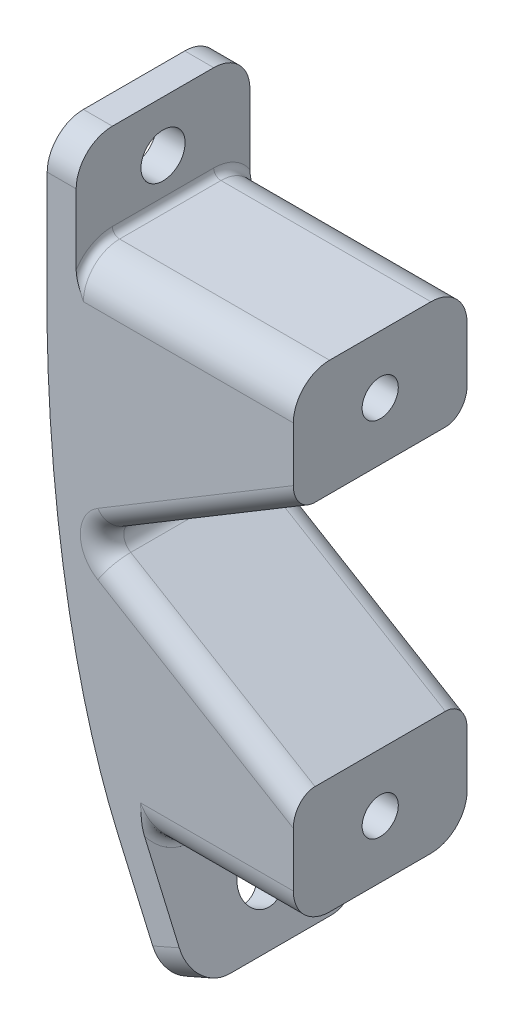
SolidWorks part; units mm, degrees
ref_plane "Front Plane" through (0, 0, 0) normal (0, 0, 1) x (1, 0, 0)
ref_plane "Top Plane" through (0, 0, 0) normal (0, 1, 0) x (1, 0, 0)
ref_plane "Right Plane" through (0, 0, 0) normal (1, 0, 0) x (0, 0, -1)
sketch "Sketch2" plane through (0, 0, 0) normal (1, 0, 0) x (0, 0, -1)
  line L0 (12, 98) -> (12, 0) construction
  line L1 (0, 0) -> (24, 0)
  line L2 (0, 0) -> (0, 98)
  line L3 (0, 98) -> (24, 98)
  line L4 (24, 0) -> (24, 98)
  line L5 (0, 49) -> (24, 49) construction
  circle A0 centre (12, 88) radius 3.05
  dimension "D3" = 6.1
  dimension "D4" = 39
  dimension "D1" = 98
  dimension "D2" = 24
extrude "Boss-Extrude1" add sketch "Sketch2" along normal blind 4
sketch "Sketch3" plane through (4, 0, 0) normal (1, 0, 0) x (0, 0, -1)
  line L0 (0, 98) -> (0, 0) construction
  line L1 (0, 82) -> (24, 82)
  line L2 (0, 82) -> (0, 16)
  line L3 (0, 16) -> (24, 16)
  line L4 (24, 82) -> (24, 16)
  line L5 (24, 0) -> (24, 98) construction
  line L6 (0, 49) -> (24, 49) construction
  line L7 (12, 98) -> (12, 0) construction
  line L8 (24, 98) -> (0, 98) construction
  line L9 (0, 0) -> (24, 0) construction
  line L10 (24, 0) -> (24, 98) construction
  dimension "D1" = 66
extrude "Boss-Extrude2" add sketch "Sketch3" along normal blind 30
sketch "Sketch13" plane through (4, 0, 0) normal (1, 0, 0) x (0, 0, -1)
  line L0 (24, 82) -> (24, 98) construction
  line L1 (0, 98) -> (24, 98)
  line L2 (0, 98) -> (0, 95)
  line L3 (0, 95) -> (24, 95)
  line L4 (24, 98) -> (24, 95)
  circle A0 centre (12, 88) radius 3.05 construction
  dimension "D1" = 7
extrude "Cut-Extrude6" cut sketch "Sketch13" against normal through all
sketch "Sketch12" plane through (4, 0, 0) normal (1, 0, 0) x (0, 0, -1)
  circle A0 centre (12, 88) radius 5.25 construction
  dimension "D1" = 10.5
sketch "Sketch4" plane through (34, 0, 0) normal (1, 0, 0) x (0, 0, -1)
  line L0 (12, 82) -> (12, 16) construction
  line L1 (24, 82) -> (0, 82) construction
  line L2 (0, 16) -> (24, 16) construction
  line L3 (0, 49) -> (24, 49) construction
  line L4 (0, 82) -> (0, 16) construction
  line L5 (24, 16) -> (24, 82) construction
  circle A0 centre (12, 74) radius 2.5
  circle A1 centre (12, 24) radius 2.5
  dimension "D1" = 5
  dimension "D2" = 50
extrude "Cut-Extrude1" cut sketch "Sketch4" against normal through all both and the other way through all
sketch "Sketch5" plane through (0, 0, 0) normal (-1, 0, 0) x (0, 0, 1)
  line L0 (-24, 47.5) -> (0, 47.5) construction
  line L1 (-9.7772, 77.85) -> (-14.2228, 77.85)
  line L2 (-14.2228, 77.85) -> (-16.4456, 74)
  line L3 (-16.4456, 74) -> (-14.2228, 70.15)
  line L4 (-14.2228, 70.15) -> (-9.7772, 70.15)
  line L5 (-9.7772, 70.15) -> (-7.5544, 74)
  line L6 (-7.5544, 74) -> (-9.7772, 77.85)
  line L7 (-24, 0) -> (-24, 95) construction
  line L8 (0, 95) -> (0, 0) construction
  line L16 (-9.7772, 27.85) -> (-14.2228, 27.85)
  line L17 (-14.2228, 27.85) -> (-16.4456, 24)
  line L18 (-16.4456, 24) -> (-14.2228, 20.15)
  line L19 (-14.2228, 20.15) -> (-9.7772, 20.15)
  line L20 (-9.7772, 20.15) -> (-7.5544, 24)
  line L21 (-7.5544, 24) -> (-9.7772, 27.85)
  circle A0 centre (-12, 74) radius 3.85 construction
  circle A2 centre (-12, 24) radius 3.85 construction
  dimension "D1" = 7.7
  dimension "D2" = 7.7
extrude "Cut-Extrude2" cut sketch "Sketch5" against normal offset from surface (26 mm away) 8 up to face at (34, 74, -14.5)
sketch "Sketch8" plane through (0, 0, 0) normal (0, 0, 1) x (1, 0, 0)
  line L0 (4, 88.0223) -> (4, -6.0183) construction
  line L1 (0, 82) -> (4, 82)
  line L2 (34, 16) -> (4, 16) construction
  line L4 (29.8923, 0) -> (0, 0)
  line L5 (0, 0) -> (0, 82)
  line L7 (29.8923, 76) -> (29.8923, 0) construction
  line L8 (29.8923, 76) -> (4, 76) construction
  line L9 (4, 82) -> (4, 76)
  line L10 (14, 16) -> (22.1491, -2.5965) construction
  line L11 (0, 95) -> (0, 0) construction
  ellipse E0 centre (29.8923, 76) end of major axis (29.8923, 0) minor radius 25.8923 (4, 76) -> (29.8923, 0) ccw
  point P23 (14, 16)
  dimension "D1" = 60
  dimension "D2" = 10
extrude "Cut-Extrude4" cut sketch "Sketch8" against normal through all
sketch "Sketch10" plane through (0, 0, 0) normal (0, 0, 1) x (1, 0, 0)
  line L6 (0, 95) -> (0, 82) construction
  line L22 (16.5831, 0.1392) -> (20.2468, 1.7446)
  line L23 (20.2468, 1.7446) -> (14, 16)
  line L24 (34, 49) -> (0, 49) construction
  line L25 (34, 82) -> (34, 16) construction
  line L28 (4, 95) -> (4, 82) construction
  line L29 (9.7204, 15.8001) -> (16.5831, 0.1392)
  line L32 (4, 82) -> (4, 76)
  line L33 (14, 16) -> (34, 16)
  line L34 (34, 16) -> (34, 82)
  line L35 (34, 82) -> (4, 82)
  line L36 (4, 82) -> (4, 76)
  line L41 (0, 82) -> (-0.0395, 77.0883)
  line L44 (4, 82) -> (0, 82)
  ellipse E0 centre (29.8923, 76) end of major axis (29.8923, 0) minor radius 25.8923 (4, 76) -> (14, 16) ccw construction
  ellipse E2 centre (29.8923, 76) end of major axis (29.8923, 0) minor radius 25.8923 (4, 76) -> (14, 16) ccw
  ellipse E3 centre (29.8923, 76) end of major axis (29.8923, 0) minor radius 25.8923 (4, 76) -> (14, 16) ccw
  spline S1 degree 3 poles (-0.0395, 77.0883) (-0.0828, 71.7041) (0.0617, 66.3402) (0.7432, 55.6552) (1.2791, 50.334) (2.4388, 42.3908) (2.8853, 39.7496) (3.9207, 34.4826) (4.5095, 31.8561) (5.8674, 26.6259) (6.6313, 24.0405) (8.1733, 19.5712) (8.9011, 17.6697) (9.7204, 15.8001) knots 0 0 0 0 0.25 0.25 0.5 0.5 0.625 0.625 0.75 0.75 0.875 0.875 0.969487 0.969487 0.969487 0.969487
  point P19 (17.4373, 8.156)
  point P30 (5.689, 49)
  dimension "D3" = 7
  dimension "D5" = 42.5
  dimension "D6" = 8.564
  dimension "D1" = 4
  dimension "D8" = 0
extrude "Boss-Extrude3" add sketch "Sketch10" against normal up to surface (24 mm away) up to face at (17.5268, 53.7205, -24)
fillet "Fillet1" radius 5 4 edges at (18.415, 0.9419, -24) (18.415, 0.9419, 0) (2, 95, -24) (2, 95, 0)
fillet "Fillet2" radius 5 4 edges at (24, 16, -24) (24, 16, 0) (19, 82, -24) (19, 82, 0)
sketch "Sketch7" plane through (0, 0, -24) normal (0, 0, -1) x (-1, 0, 0)
  line L0 (-34, 66) -> (-5.689, 49)
  line L1 (-34, 21) -> (-34, 77) construction
  line L3 (-5.689, 49) -> (-34, 32)
  line L4 (-34, 32) -> (-34, 66)
  line L5 (-34, 49) -> (-5.689, 49) construction
  dimension "D1" = 34
extrude "Cut-Extrude3" cut sketch "Sketch7" against normal through all
sketch "Sketch11" plane through (13.9629, 6.1186, 0) normal (-0.9159, -0.4014, 0) x (0, 0, 1)
  line L0 (-12, -6.5284) -> (-12, 0.4716) construction
  line L1 (-19, -6.5284) -> (-5, -6.5284) construction
  line L2 (0, 0.4716) -> (-12, 0.4716) construction
  circle A0 centre (-12, 0.4716) radius 3
  dimension "D1" = 6
extrude "Cut-Extrude5" cut sketch "Sketch11" against normal up to next
fillet "Fillet3" [suppressed] radius 1
fillet "Fillet4" radius 2 1 edges at (5.689, 49, -12)
fillet "Fillet5" radius 3 6 edges at (21.2723, 39.6427, -24) (7.5741, 49, -24) (21.2723, 39.6427, 0) (7.5741, 49, 0) (21.2723, 58.3573, -24) (21.2723, 58.3573, 0)
sketch "Sketch14" plane through (34, 0, 0) normal (1, 0, 0) x (0, 0, -1)
  circle A2 centre (12, 74) radius 2.5 construction
  circle A4 centre (12, 24) radius 2.5 construction
  circle A5 centre (12, 74) radius 2.5
  circle A6 centre (12, 24) radius 2.5
extrude "Cut-Extrude7" cut sketch "Sketch14" against normal through all
sketch "Sketch15" plane through (26, 0, 0) normal (-1, 0, 0) x (0, 0, 1)
  line L6 (-7.5544, 24) -> (-9.7772, 27.85)
  line L7 (-9.7772, 27.85) -> (-14.2228, 27.85)
  line L8 (-14.2228, 27.85) -> (-16.4456, 24)
  line L9 (-16.4456, 24) -> (-14.2228, 20.15)
  line L10 (-14.2228, 20.15) -> (-9.7772, 20.15)
  line L11 (-9.7772, 20.15) -> (-7.5544, 24)
  line L12 (-7.5544, 24) -> (-9.7772, 27.85)
  line L13 (-9.7772, 27.85) -> (-14.2228, 27.85)
  line L14 (-14.2228, 27.85) -> (-16.4456, 24)
  line L15 (-16.4456, 24) -> (-14.2228, 20.15)
  line L16 (-14.2228, 20.15) -> (-9.7772, 20.15)
  line L17 (-9.7772, 20.15) -> (-7.5544, 24)
  line L18 (-7.5544, 74) -> (-9.7772, 77.85)
  line L19 (-9.7772, 77.85) -> (-14.2228, 77.85)
  line L20 (-14.2228, 77.85) -> (-16.4456, 74)
  line L21 (-16.4456, 74) -> (-14.2228, 70.15)
  line L22 (-14.2228, 70.15) -> (-9.7772, 70.15)
  line L23 (-9.7772, 70.15) -> (-7.5544, 74)
  line L24 (-7.5544, 74) -> (-9.7772, 77.85)
  line L25 (-9.7772, 77.85) -> (-14.2228, 77.85)
  line L26 (-14.2228, 77.85) -> (-16.4456, 74)
  line L27 (-16.4456, 74) -> (-14.2228, 70.15)
  line L28 (-14.2228, 70.15) -> (-9.7772, 70.15)
  line L29 (-9.7772, 70.15) -> (-7.5544, 74)
  dimension "D1" = 0
  dimension "D2" = 0
extrude "Cut-Extrude8" cut sketch "Sketch15" along normal through all
fillet "Fillet6" radius 1 6 edges at (4, 80.5355, -22.5355) (4, 82, -12) (13.3583, 17.4645, -22.5355) (14, 16, -12) (4, 80.5355, -1.4645) (13.3583, 17.4645, -1.4645)
equation "\"D2@Sketch5\"=\"D1@Sketch5\""
